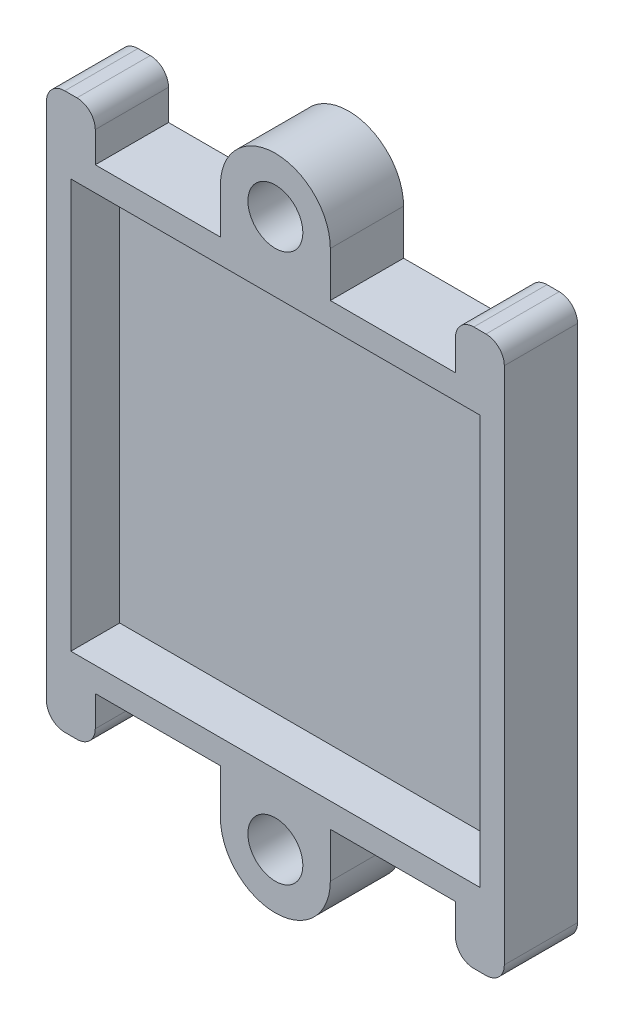
SolidWorks part; units mm, degrees
ref_plane "Спереди" through (0, 0, 0) normal (0, 0, 1) x (1, 0, 0)
ref_plane "Сверху" through (0, 0, 0) normal (0, 1, 0) x (1, 0, 0)
ref_plane "Справа" through (0, 0, 0) normal (1, 0, 0) x (0, 0, -1)
sketch "Эскиз1" plane through (0, 0, 0) normal (0, 0, 1) x (1, 0, 0)
  line L1 (0, 0) -> (75, 0)
  line L2 (0, 0) -> (0, 75)
  line L3 (0, 75) -> (75, 75)
  line L4 (75, 0) -> (75, 75)
  dimension "D1" = 75
  dimension "D2" = 75
extrude "Бобышка-Вытянуть1" add sketch "Эскиз1" along normal blind 4
sketch "Эскиз2" plane through (0, 0, 4) normal (0, 0, 1) x (1, 0, 0)
  line L0 (4, 71) -> (71, 71)
  line L1 (0, 75) -> (75, 75)
  line L2 (0, 75) -> (0, 0)
  line L3 (0, 0) -> (75, 0)
  line L4 (75, 75) -> (75, 0)
  line L5 (4, 4) -> (4, 71)
  line L6 (4, 4) -> (71, 4)
  line L7 (71, 4) -> (71, 71)
  dimension "D1" = 4
  dimension "D2" = 4
  dimension "D3" = 4
  dimension "D4" = 4
extrude "Бобышка-Вытянуть2" add sketch "Эскиз2" along normal blind 8
sketch "Эскиз3" plane through (0, 75, 0) normal (0, 1, 0) x (1, 0, 0)
  line L0 (75, -12) -> (0, -12) construction
  line L1 (0, 0) -> (8, 0)
  line L2 (0, 0) -> (0, -12)
  line L3 (0, -12) -> (8, -12)
  line L4 (8, 0) -> (8, -12)
  dimension "D1" = 8
extrude "Бобышка-Вытянуть3" add sketch "Эскиз3" along normal blind 8
ref_plane "Плоскость4" through (37.5, 0, 0) normal (1, 0, 0) x (0, 0, -1)
mirror "Зеркальное отражение1" about plane through (37.5, 0, 0) normal (1, 0, 0) of "Бобышка-Вытянуть3"
ref_plane "Плоскость5" through (0, 37.5, 0) normal (0, 1, 0) x (1, 0, 0)
mirror "Зеркальное отражение2" about plane through (0, 37.5, 0) normal (0, 1, 0) of "Зеркальное отражение1", "Бобышка-Вытянуть3", "Бобышка-Вытянуть2"
fillet "Скругление4" radius 3 4 edges at (67, 83, 6) (75, 83, 6) (0, 83, 6) (8, 83, 6)
fillet "Скругление5" radius 3 4 edges at (75, -8, 6) (67, -8, 6) (8, -8, 6) (0, -8, 6)
sketch "Эскиз4" plane through (0, 0, 12) normal (0, 0, 1) x (1, 0, 0)
  line L0 (28.5, 75) -> (28.5, 82.3842)
  line L1 (67, 75) -> (8, 75) construction
  line L2 (46.5, 75) -> (46.5, 82.3842)
  line L4 (37.5, 75) -> (37.5, 84.7724) construction
  line L5 (28.5, 75) -> (46.5, 75)
  arc A2 (28.5, 82.3842) -> (46.5, 82.3842) centre (37.5, 82.3842) cw
  circle A3 centre (37.5, 82.3842) radius 4.5
  dimension "D3" = 9
  dimension "D1" = 9
extrude "Бобышка-Вытянуть4" add sketch "Эскиз4" against normal up to surface (12 mm away) up to face at (37.5, 37.5, 0)
mirror "Зеркальное отражение3" about plane through (0, 37.5, 0) normal (0, 1, 0) of "Бобышка-Вытянуть4"
